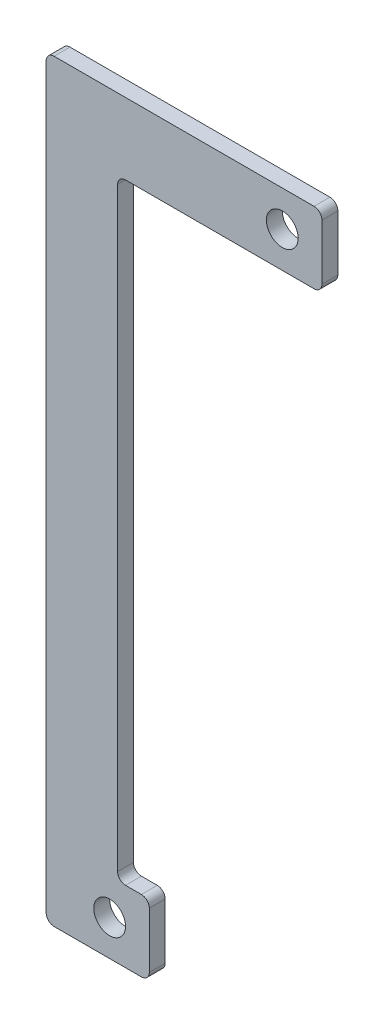
SolidWorks part; units mm, degrees
ref_plane "Front Plane" through (0, 0, 0) normal (0, 0, 1) x (1, 0, 0)
ref_plane "Top Plane" through (0, 0, 0) normal (0, 1, 0) x (1, 0, 0)
ref_plane "Right Plane" through (0, 0, 0) normal (1, 0, 0) x (0, 0, -1)
sketch "Sketch1" plane through (0, 0, 0) normal (0, 0, 1) x (1, 0, 0)
  line L0 (13, 8) -> (13, 1)
  line L1 (12, 0) -> (1, 0)
  line L2 (0, 1) -> (0, 94)
  line L3 (1, 95) -> (33.76, 95)
  line L4 (34.76, 94) -> (34.76, 87)
  line L5 (33.76, 86) -> (10, 86)
  line L6 (9, 85) -> (9, 10)
  line L7 (10, 9) -> (12, 9)
  line L8 (55, 0) -> (-55, 0) construction
  line L9 (29.76, 90.5) -> (29.76, 86) construction
  line L10 (29.76, 90.5) -> (29.76, 95) construction
  line L11 (10, 9) -> (0, 9) construction
  line L12 (8, 9) -> (8, 4.5) construction
  line L13 (8, 4.5) -> (8, 0) construction
  arc A0 (0, 94) -> (1, 95) centre (1, 94) cw
  arc A1 (13, 1) -> (12, 0) centre (12, 1) cw
  arc A2 (1, 0) -> (0, 1) centre (1, 1) cw
  arc A3 (9, 10) -> (10, 9) centre (10, 10) ccw
  arc A4 (13, 8) -> (12, 9) centre (12, 8) ccw
  arc A5 (10, 86) -> (9, 85) centre (10, 85) ccw
  arc A6 (34.76, 87) -> (33.76, 86) centre (33.76, 87) cw
  arc A7 (33.76, 95) -> (34.76, 94) centre (33.76, 94) cw
  circle A8 centre (29.76, 90.5) radius 2
  circle A9 centre (8, 4.5) radius 2
  dimension "D1" = 1
  dimension "D2" = 1
  dimension "D10" = 4
  dimension "D13" = 4
  dimension "D3" = 9
  dimension "D4" = 4
  dimension "D5" = 9
  dimension "D6" = 9
  dimension "D7" = 95
  dimension "D8" = 34.76
  dimension "D9" = 0
  dimension "D11" = 5
  dimension "D12" = 5
extrude "Boss-Extrude1" add sketch "Sketch1" along normal blind 2
